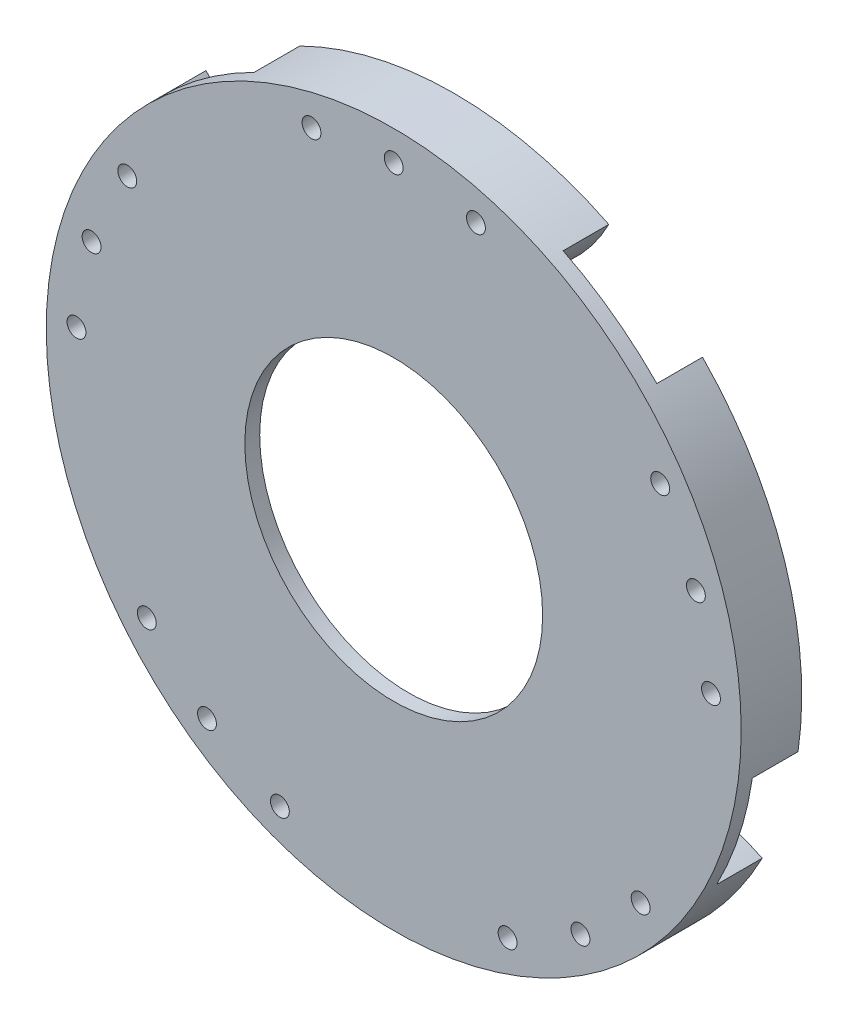
SolidWorks part; units mm, degrees
ref_plane "Front Plane" through (0, 0, 0) normal (0, 0, 1) x (1, 0, 0)
ref_plane "Top Plane" through (0, 0, 0) normal (0, 1, 0) x (1, 0, 0)
ref_plane "Right Plane" through (0, 0, 0) normal (1, 0, 0) x (0, 0, -1)
ref_axis "X-Axis" through (-88.99, 0, 0) along (1, 0, 0)
ref_axis "Y-Axis" through (0, 55, 0) along (0, -1, 0)
ref_axis "Z-Axis" through (0, 0, -88.99) along (0, 0, 1)
sketch "Sketch1" plane through (0, 0, 0) normal (0, 0, 1) x (1, 0, 0)
  circle A0 centre (0, 0) radius 35
  dimension "D1" = 70
extrude "Boss-Extrude1" add sketch "Sketch1" along normal blind 1.5
sketch "Sketch2" plane through (0, 0, 0) normal (0, 0, -1) x (-1, 0, 0)
  line L0 (0, 0) -> (0, 39.35) construction
  circle A0 centre (0, 39.35) radius 17.5 construction
  arc A2 (-15.5639, 31.3491) -> (15.5639, 31.3491) centre (0, 39.35) ccw
  circle A3 centre (0, 0) radius 35
  arc A4 (15.5639, 31.3491) -> (-15.5639, 31.3491) centre (0, 0) ccw
  dimension "D2" = 35
  dimension "D1" = 39.35
  dimension "D3" = 0
extrude "Boss-Extrude2" add sketch "Sketch2" along normal blind 4.6
sketch "Sketch4" plane through (0, 0, 1.5) normal (0, 0, 1) x (1, 0, 0)
  line L0 (0, 0) -> (0, 32) construction
  circle A0 centre (0, 32) radius 0.95
  dimension "D1" = 1.9
  dimension "D2" = 32
extrude "Cut-Extrude2" cut sketch "Sketch4" against normal through all
pattern_circular "CirPattern5" count 2 over 15 about axis through (0, 0, -88.99) along (0, 0, 1) of "Cut-Extrude2"
pattern_circular "CirPattern6" count 2 over 15 about axis through (0, 0, -88.99) along (0, 0, 1) of "Cut-Extrude2" reverse direction yes
pattern_circular "CirPattern1" count 5 over 360 about axis through (0, 0, -88.99) along (0, 0, 1) of "Boss-Extrude2", "Cut-Extrude2", "CirPattern5", "CirPattern6"
sketch "Sketch3" plane through (0, 0, 1.5) normal (0, 0, 1) x (1, 0, 0)
  circle A0 centre (0, 0) radius 15
  dimension "D1" = 30
extrude "Cut-Extrude1" cut sketch "Sketch3" against normal through all
sketch "Sketch5" plane through (0, 0, -4.6) normal (0, 0, -1) x (-1, 0, 0)
  circle A0 centre (0, 0) radius 30
  circle A1 centre (0, 0) radius 29
  dimension "D1" = 1
extrude "Boss-Extrude3" [suppressed] add sketch "Sketch5" against normal blind 1
